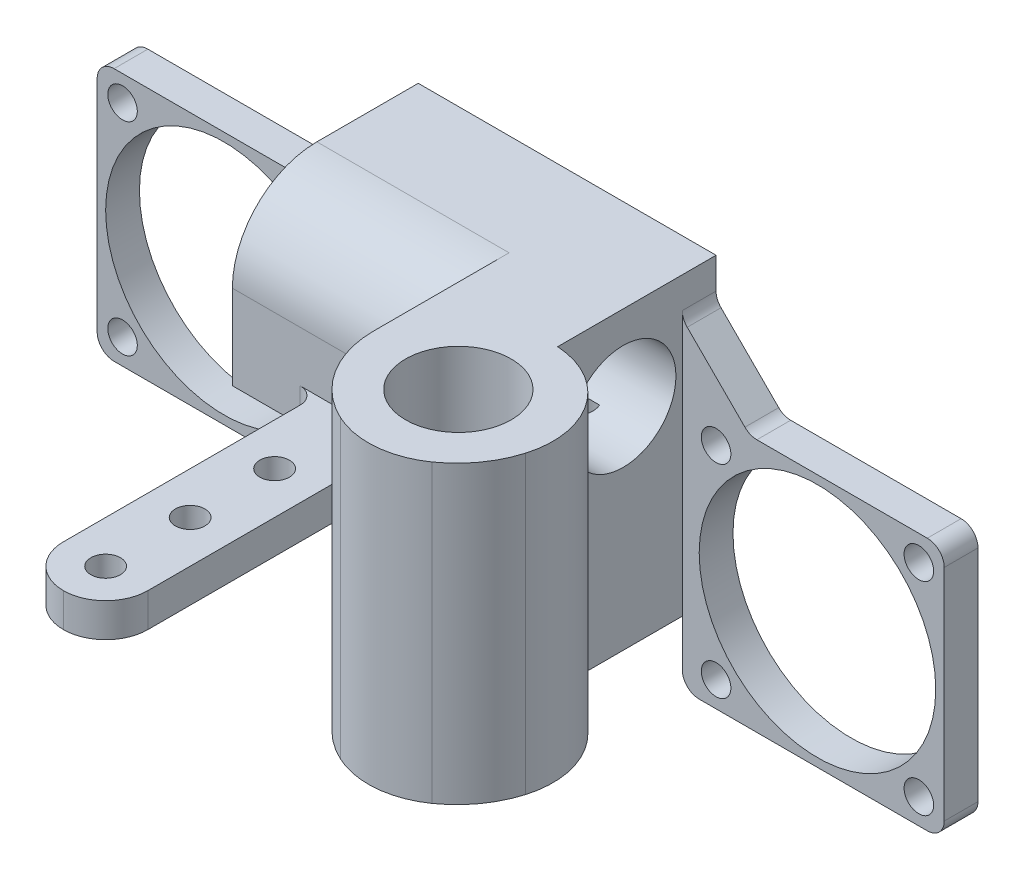
SolidWorks part; units mm, degrees
ref_plane "Спереди" through (0, 0, 0) normal (0, 0, 1) x (1, 0, 0)
ref_plane "Сверху" through (0, 0, 0) normal (0, 1, 0) x (1, 0, 0)
ref_plane "Справа" through (0, 0, 0) normal (1, 0, 0) x (0, 0, -1)
ref_plane "Плоскость4" through (0, 35, 0) normal (0, 1, 0) x (1, 0, 0)
sketch "Эскиз1" plane through (0, 35, 0) normal (0, 1, 0) x (1, 0, 0)
  line L0 (35, 0) -> (13, 0)
  line L1 (13, 0) -> (13, -28)
  line L2 (35, -28.1678) -> (35, 0)
  arc A0 (13, -28) -> (25, -40) centre (25, -28) ccw
  arc A1 (25, -40) -> (35, -28.1678) centre (23, -28.1678) ccw
extrude "Бобышка-Вытянуть1" add sketch "Эскиз1" against normal blind 35
sketch "Эскиз2" plane through (13, 0, 0) normal (-1, 0, 0) x (0, 0, 1)
  line L0 (22, 0) -> (0, 0)
  line L1 (0, 0) -> (0, 35)
  line L2 (0, 35) -> (22, 35)
  line L3 (22, 35) -> (22, 0)
extrude "Бобышка-Вытянуть2" add sketch "Эскиз2" along normal blind 22.75
sketch "Эскиз3" plane through (-9.75, 0, 0) normal (-1, 0, 0) x (0, 0, 1)
  line L0 (11, 15) -> (0, 15)
  line L1 (0, 15) -> (0, 0)
  line L2 (0, 0) -> (11, 0)
  line L3 (11, 0) -> (11, 15)
  dimension "D1" = 20
  dimension "D2" = 15
  dimension "D3" = 11
extrude "Вырез-Вытянуть1" cut sketch "Эскиз3" against normal blind 32
hole_wizard "Диаметр отверстия Ø12.5 (12.5)1" positions "Эскиз5" profile "Эскиз4" hole size "Ø12.5" standard "Ansi Metric"
sketch "Эскиз5" plane through (0, 35, 0) normal (0, 1, 0) x (1, 0, 0)
  point P0 (24, -29)
sketch "Эскиз4" plane through (24, 35, 29) normal (1, 0, 0) x (0, 0, 1)
  line L0 (0, 0) -> (0, 35)
  line L1 (0, 35) -> (6.25, 35)
  line L2 (6.25, 35) -> (6.25, 0)
  line L5 (6.25, 0) -> (0, 0)
  line L11 (0, -6.35) -> (0, 107.95) construction
  dimension "Диаметр сквозного отверстия" = 12.5
  dimension "Глубина сквозного отверстия" = 35
hole_wizard "Диаметр отверстия Ø12.5 (12.5)2" positions "Эскиз7" profile "Эскиз6" hole size "Ø12.5" standard "Ansi Metric"
sketch "Эскиз7" plane through (35, 0, 0) normal (1, 0, 0) x (0, 0, -1)
  line L0 (55, 35) -> (-55, 35) construction
  point P0 (-11, 25)
  dimension "D1" = 10
sketch "Эскиз6" plane through (35, 25, 11) normal (0, 1, 0) x (0, 0, -1)
  line L0 (0, 0) -> (0, 44.75)
  line L1 (0, 44.75) -> (6.25, 44.75)
  line L2 (6.25, 44.75) -> (6.25, 0)
  line L5 (6.25, 0) -> (0, 0)
  line L11 (0, -6.35) -> (0, 107.95) construction
  dimension "Диаметр сквозного отверстия" = 12.5
  dimension "Глубина сквозного отверстия" = 44.75
hole_wizard "Диаметр отверстия Ø3.5 (3.5)1" positions "Эскиз9" profile "Эскиз8" hole size "Ø3.5" standard "Ansi Metric"
sketch "Эскиз9" plane through (0, 15, 0) normal (0, -1, 0) x (-1, 0, 0)
  line L0 (9.75, -11) -> (9.75, 0) construction
  point P0 (-17.25, -7)
  point P1 (6.75, -7)
  point P2 (-12.25, -7)
  point P3 (1.75, -7)
  dimension "D1" = 3
  dimension "D2" = 5
  dimension "D3" = 14
  dimension "D4" = 5
sketch "Эскиз8" plane through (17.25, 15, 7) normal (1, 0, 0) x (0, 0, -1)
  line L0 (0, 0) -> (0, 5)
  line L1 (0, 5) -> (1.75, 5)
  line L2 (1.75, 5) -> (1.75, 0)
  line L5 (1.75, 0) -> (0, 0)
  line L10 (0, 5) -> (-1.75, 5) construction
  line L11 (0, -6.35) -> (0, 107.95) construction
  dimension "Диаметр отверстия" = 3.5
  dimension "Глубина отверстия" = 5
  dimension "Угол заточки сверла" = 180
sketch "Эскиз10" plane through (0, 0, 0) normal (0, -1, 0) x (1, 0, 0)
  line L1 (35, 0) -> (25.5, 0)
  line L2 (35, 0) -> (35, 18.75)
  line L3 (35, 18.75) -> (25.5, 18.75)
  line L4 (25.5, 0) -> (25.5, 18.75)
  circle A0 centre (24, 29) radius 6.25 construction
  dimension "D1" = 9.5
  dimension "D2" = 10.25
extrude "Вырез-Вытянуть2" cut sketch "Эскиз10" against normal through all
sketch "Эскиз11" plane through (0, 0, 0) normal (0, -1, 0) x (1, 0, 0)
  line L0 (22.25, 11) -> (-9.75, 11) construction
  line L1 (-9.75, 11) -> (13, 11)
  line L2 (-9.75, 11) -> (-9.75, 22)
  line L3 (-9.75, 22) -> (13, 22)
  line L4 (13, 11) -> (13, 22)
  line L5 (-9.75, 22) -> (13, 22) construction
  line L6 (-9.75, 11) -> (-9.75, 22) construction
  dimension "D1" = 0
  dimension "D2" = 0
extrude "Вырез-Вытянуть3" cut sketch "Эскиз11" against normal up to surface (15 mm away) up to face at (17.25, 15, 5.25)
fillet "Скругление2" radius 10 1 edges at (25, 17.5, 40)
sketch "Эскиз13" plane through (25.5, 0, 0) normal (1, 0, 0) x (0, 0, -1)
  line L12 (-4, -7.5) -> (0, -7.5)
  line L13 (-4, -7.5) -> (-4, 22.5)
  line L14 (-4, 22.5) -> (0, 22.5)
  line L15 (0, -7.5) -> (0, 22.5)
  circle A1 centre (-11, 25) radius 6.25 construction
  dimension "D1" = 30
  dimension "D3" = 7
  dimension "D4" = 4
extrude "Бобышка-Вытянуть3" add sketch "Эскиз13" along normal blind 31 separate body
hole_wizard "Диаметр отверстия Ø3.5 (3.5)2" positions "Эскиз15" profile "Эскиз16" hole size "Ø3.5" standard "ISO" end condition through all
sketch "Эскиз15" plane through (0, 0, 4) normal (0, 0, 1) x (1, 0, 0)
  line L0 (56.5, -7.5) -> (25.5, -7.5) construction
  line L1 (56.5, 22.5) -> (25.5, 22.5) construction
  line L2 (25.5, 22.5) -> (25.5, -7.5) construction
  line L3 (56.5, 22.5) -> (56.5, -7.5) construction
  point P0 (29.5, -4.5)
  point P2 (29.5, 19.5)
  point P4 (53.5, 19.5)
  point P6 (53.5, -4.5)
  dimension "D1" = 3
  dimension "D2" = 3
  dimension "D3" = 4
  dimension "D4" = 4
  dimension "D5" = 3
  dimension "D6" = 3
  dimension "D7" = 3
  dimension "D8" = 3
sketch "Эскиз16" plane through (29.5, -4.5, 4) normal (1, 0, 0) x (0, -1, 0)
  line L0 (0, 0) -> (0, 4)
  line L1 (0, 4) -> (1.75, 4)
  line L2 (1.75, 4) -> (1.75, 0)
  line L5 (1.75, 0) -> (0, 0)
  line L11 (0, -6.35) -> (0, 107.95) construction
  dimension "Диаметр сквозного отверстия" = 3.5
  dimension "Глубина сквозного отверстия" = 4
sketch "Эскиз17" plane through (0, 0, 4) normal (0, 0, 1) x (1, 0, 0)
  line L0 (56.5, 22.5) -> (56.5, -7.5) construction
  line L3 (56.5, -7.5) -> (25.5, -7.5) construction
  circle A0 centre (41.5, 7.5) radius 14
  dimension "D1" = 28
  dimension "D2" = 15
  dimension "D3" = 15
extrude "Вырез-Вытянуть4" cut sketch "Эскиз17" against normal through all
sketch "Эскиз19" plane through (-9.75, 0, 0) normal (-1, 0, 0) x (0, 0, 1)
  line L0 (0, 35) -> (0, 15) construction
  line L1 (4, 22.5) -> (0, 22.5)
  line L2 (4, 22.5) -> (4, -7.5)
  line L3 (4, -7.5) -> (0, -7.5)
  line L4 (0, 22.5) -> (0, -7.5)
  dimension "D3" = 0
  dimension "D1" = 4
  dimension "D2" = 30
extrude "Бобышка-Вытянуть5" add sketch "Эскиз19" along normal blind 34
sketch "Эскиз20" plane through (0, 0, 4) normal (0, 0, 1) x (1, 0, 0)
  line L0 (-43.75, -7.5) -> (-43.75, 22.5) construction
  line L2 (-43.75, -7.5) -> (-9.75, -7.5) construction
  circle A0 centre (-28.75, 7.5) radius 14
  dimension "D1" = 15
  dimension "D2" = 15
extrude "Вырез-Вытянуть5" cut sketch "Эскиз20" against normal through all
hole_wizard "Диаметр отверстия Ø3.5 (3.5)3" positions "Эскиз21" profile "Эскиз22" hole size "Ø3.5" standard "ISO" end condition through all
sketch "Эскиз21" plane through (0, 0, 4) normal (0, 0, 1) x (1, 0, 0)
  line L0 (-9.75, 15) -> (-9.75, 22.5) construction
  line L1 (-9.75, -7.5) -> (-9.75, 15) construction
  line L2 (-43.75, 22.5) -> (-9.75, 22.5) construction
  line L3 (-43.75, -7.5) -> (-9.75, -7.5) construction
  line L5 (-43.75, -7.5) -> (-43.75, 22.5) construction
  point P0 (-16.75, 19.5)
  point P2 (-16.75, -4.5)
  point P4 (-40.75, -4.5)
  point P6 (-40.75, 19.5)
  dimension "D1" = 7
  dimension "D2" = 7
  dimension "D3" = 3
  dimension "D4" = 3
  dimension "D5" = 3
  dimension "D6" = 3
  dimension "D7" = 3
  dimension "D8" = 3
sketch "Эскиз22" plane through (-16.75, 19.5, 4) normal (1, 0, 0) x (0, -1, 0)
  line L0 (0, 0) -> (0, 4)
  line L1 (0, 4) -> (1.75, 4)
  line L2 (1.75, 4) -> (1.75, 0)
  line L5 (1.75, 0) -> (0, 0)
  line L11 (0, -6.35) -> (0, 107.95) construction
  dimension "Диаметр сквозного отверстия" = 3.5
  dimension "Глубина сквозного отверстия" = 4
sketch "Эскиз24" plane through (0, 0, 4) normal (0, 0, 1) x (1, 0, 0)
  line L0 (-9.75, 30.5) -> (-17.75, 22.5)
  line L1 (-9.75, 22.5) -> (-17.75, 22.5)
  line L2 (-9.75, 22.5) -> (-9.75, 30.5)
extrude "Бобышка-Вытянуть6" add sketch "Эскиз24" against normal up to surface (4 mm away) up to face at (-15, 19.5, 0)
sketch "Эскиз25" plane through (0, 0, 4) normal (0, 0, 1) x (1, 0, 0)
  line L0 (33.5, 22.5) -> (25.5, 30.5)
  line L1 (25.5, 22.5) -> (33.5, 22.5)
  line L2 (25.5, 22.5) -> (25.5, 30.5)
extrude "Бобышка-Вытянуть7" add sketch "Эскиз25" against normal up to surface (4 mm away) up to face at (55.5, 7.5, 0)
sketch "Эскиз26" plane through (0, 0, 22) normal (0, 0, 1) x (1, 0, 0)
  line L0 (13, 15) -> (-9.75, 15) construction
  line L1 (0.25, 15) -> (10.25, 15)
  line L2 (0.25, 15) -> (0.25, 19)
  line L3 (0.25, 19) -> (10.25, 19)
  line L4 (10.25, 15) -> (10.25, 19)
  line L6 (-9.75, 15) -> (-9.75, 35) construction
  dimension "D1" = 10
  dimension "D2" = 10
  dimension "D3" = 4
extrude "Бобышка-Вытянуть8" add sketch "Эскиз26" along normal blind 35
hole_wizard "Диаметр отверстия Ø3.5 (3.5)4" positions "Эскиз28" profile "Эскиз29" hole size "Ø3.5" standard "ISO" end condition through all
sketch "Эскиз28" plane through (0, 15, 0) normal (0, -1, 0) x (-1, 0, 0)
  line L0 (-0.25, -57) -> (-0.25, -22) construction
  line L2 (-0.25, -57) -> (-10.25, -57) construction
  point P0 (-5.25, -52)
  point P25 (-5.25, -42)
  point P27 (-5.25, -32)
  dimension "D1" = 5
  dimension "D2" = 5
  dimension "D3" = 3
sketch "Эскиз29" plane through (5.25, 15, 52) normal (1, 0, 0) x (0, 0, -1)
  line L0 (0, 0) -> (0, 20)
  line L1 (0, 20) -> (1.75, 20)
  line L2 (1.75, 20) -> (1.75, 0)
  line L5 (1.75, 0) -> (0, 0)
  line L11 (0, -6.35) -> (0, 107.95) construction
  dimension "Диаметр сквозного отверстия" = 3.5
  dimension "Глубина сквозного отверстия" = 20
fillet "Скругление7" radius 2 2 edges at (10.25, 17, 22) (0.25, 17, 22)
fillet "Скругление9" radius 5 2 edges at (0.25, 17, 57) (10.25, 17, 57)
fillet "Скругление10" radius 10 1 edges at (35, 17.5, 18.75)
fillet "Скругление12" radius 10 1 edges at (1.625, 35, 22)
fillet "Скругление13" radius 2 5 edges at (-9.75, -7.5, 2) (-43.75, -7.5, 2) (-43.75, 22.5, 2) (-17.75, 22.5, 2) (-9.75, 30.5, 2)
fillet "Скругление14" radius 2 5 edges at (25.5, 30.5, 2) (33.5, 22.5, 2) (56.5, 22.5, 2) (56.5, -7.5, 2) (25.5, -7.5, 2)
sketch "Эскиз32" plane through (0, 0, 4) normal (0, 0, 1) x (1, 0, 0)
  line L0 (-9.75, -5.5) -> (-9.75, 15) construction
  line L1 (-9.75, 15) -> (-9.75, 31.3284) construction
  line L2 (-9.75, 2.2703) -> (-9.75, 15)
  arc A0 (-9.75, 15) -> (-9.75, 2.2703) centre (6.4963, 8.6352) ccw
extrude "Вырез-Вытянуть6" cut sketch "Эскиз32" against normal through all
sketch "Эскиз33" plane through (0, 0, 0) normal (0, -1, 0) x (1, 0, 0)
  line L0 (13, 22) -> (13, 11)
  line L1 (22.25, 11) -> (13, 11) construction
  line L2 (22.25, 11) -> (13, 11) construction
  line L3 (13, 11) -> (22.25, 11)
  arc A0 (13, 22) -> (22.25, 11) centre (8.9387, 9.1956) cw
extrude "Вырез-Вытянуть7" cut sketch "Эскиз33" against normal up to surface (15 mm away) up to face at (5.25, 15, 50.25)
fillet "Скругление15" radius 10 1 edges at (13, 7.5, 22)
